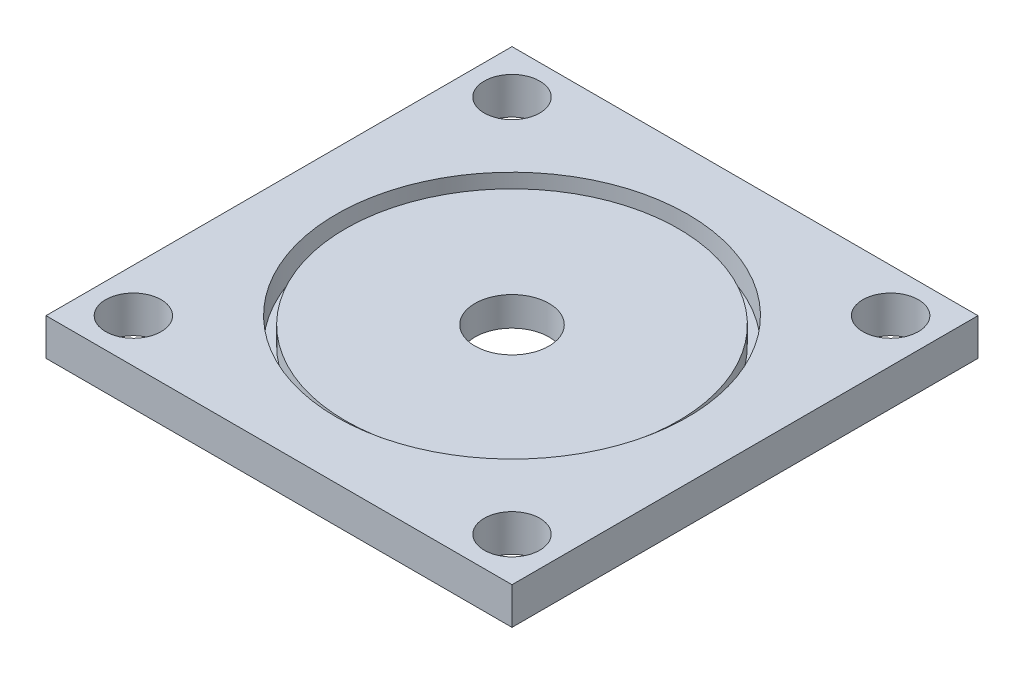
SolidWorks part; units mm, degrees
ref_plane "Front Plane" through (0, 0, 0) normal (0, 0, 1) x (1, 0, 0)
ref_plane "Top Plane" through (0, 0, 0) normal (0, 1, 0) x (1, 0, 0)
ref_plane "Right Plane" through (0, 0, 0) normal (1, 0, 0) x (0, 0, -1)
sketch "plateOutline" plane through (0, 0, 0) normal (0, 1, 0) x (1, 0, 0)
  line L1 (-40, -40) -> (40, -40)
  line L2 (-40, -40) -> (-40, 40)
  line L3 (-40, 40) -> (40, 40)
  line L4 (40, -40) -> (40, 40)
  line L5 (-40, -40) -> (40, 40) construction
  line L6 (-40, 40) -> (40, -40) construction
  line L7 (-40, -40) -> (40, -40) construction
  line L8 (-40, -40) -> (-40, 40) construction
  line L9 (-40, 40) -> (40, 40) construction
  line L10 (40, -40) -> (40, 40) construction
  point P0 (0, 0)
  dimension "D1" = 80
sketch "railGuides" plane through (0, 0, 0) normal (0, 1, 0) x (1, 0, 0)
  line L1 (-32.5, -32.5) -> (32.5, -32.5) construction
  line L2 (-32.5, -32.5) -> (-32.5, 32.5) construction
  line L3 (-32.5, 32.5) -> (32.5, 32.5) construction
  line L4 (32.5, -32.5) -> (32.5, 32.5) construction
  line L6 (-40, 40) -> (-25, 25) construction
  line L7 (40, 40) -> (25, 25) construction
  line L8 (25, -25) -> (40, -40) construction
  line L9 (-40, -40) -> (-25, -25) construction
  line L10 (-40, 40) -> (-25, 25) construction
  circle A0 centre (-32.5, 32.5) radius 4.7625
  circle A1 centre (32.5, 32.5) radius 4.7625
  circle A2 centre (32.5, -32.5) radius 4.7625
  circle A3 centre (-32.5, -32.5) radius 4.7625
sketch "FuelGrainMounting" plane through (0, 0, 0) normal (0, 1, 0) x (1, 0, 0)
  circle A0 centre (0, 0) radius 30.1625
sketch "GasIntake" plane through (0, 0, 0) normal (0, 1, 0) x (1, 0, 0)
  line L0 (-40, 40) -> (40, -40) construction
  circle A0 centre (0, 0) radius 6.35
extrude "Boss-Extrude1" add sketch "plateOutline" along normal blind 6.35 contours L3 L4 L1 L2
extrude "Cut-Extrude1" cut sketch "railGuides" along normal blind 10
extrude "Cut-Extrude2" cut sketch "FuelGrainMounting" along normal blind 5 from offset 5
extrude "Cut-Extrude3" cut sketch "GasIntake" along normal blind 5
sketch "Sketch1" plane through (0, 0, 0) normal (0, 1, 0) x (1, 0, 0)
  circle A0 centre (0, 0) radius 28.575
  circle A2 centre (0, 0) radius 30.1625
  dimension "D1" = 60.325
  dimension "D2" = 57.15
extrude "Cut-Extrude4" cut sketch "Sketch1" against normal blind 3.175 from offset 5
